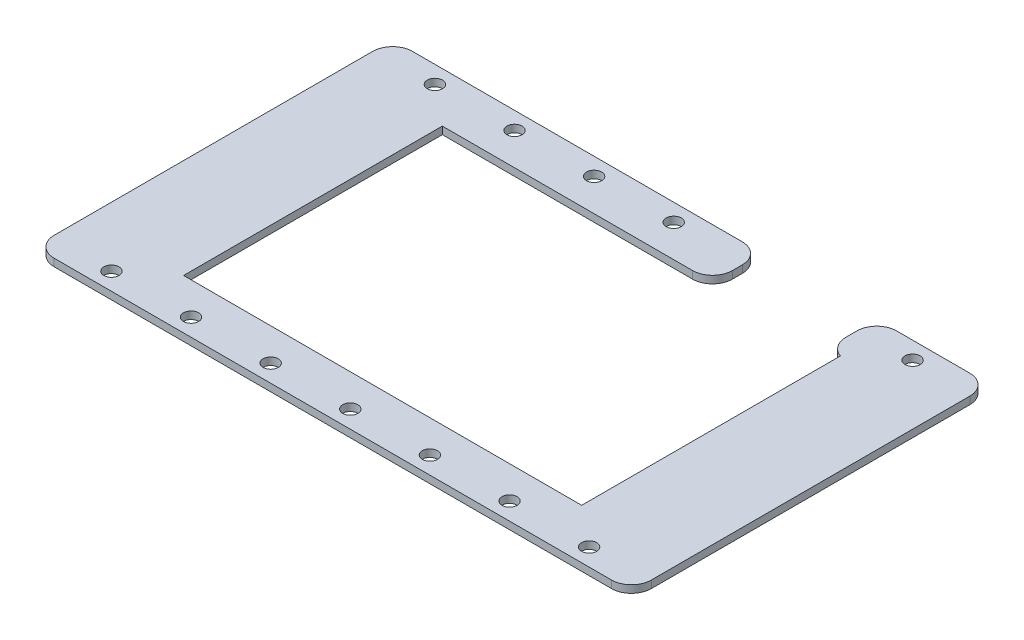
SolidWorks part; units mm, degrees
ref_plane "Front Plane" through (0, 0, 0) normal (0, 0, 1) x (1, 0, 0)
ref_plane "Top Plane" through (0, 0, 0) normal (0, 1, 0) x (1, 0, 0)
ref_plane "Right Plane" through (0, 0, 0) normal (1, 0, 0) x (0, 0, -1)
sketch "Sketch1" plane through (0, 0, 0) normal (0, 1, 0) x (1, 0, 0)
  line L0 (-95.25, -46.0375) -> (95.25, -46.0375) construction
  line L1 (95.25, -57.15) -> (-95.25, -57.15)
  line L2 (95.25, -51.5937) -> (-95.25, -51.5937) construction
  line L3 (95.25, 57.15) -> (-95.25, 57.15)
  line L4 (-95.25, -57.15) -> (-95.25, 57.15)
  line L5 (95.25, -57.15) -> (-95.25, 57.15) construction
  line L6 (95.25, 57.15) -> (-95.25, -57.15) construction
  line L7 (63.5, 41.275) -> (-63.5, 41.275)
  line L8 (63.5, 41.275) -> (63.5, -41.275)
  line L9 (63.5, -41.275) -> (-63.5, -41.275)
  line L10 (-63.5, 41.275) -> (-63.5, -41.275)
  line L11 (63.5, 41.275) -> (-63.5, -41.275) construction
  line L12 (63.5, -41.275) -> (-63.5, 41.275) construction
  line L13 (95.25, -57.15) -> (95.25, 57.15)
  line L14 (-95.25, -57.15) -> (-95.25, -46.0375) construction
  line L15 (95.25, -46.0375) -> (95.25, -57.15) construction
  line L16 (-76.2, -51.5937) -> (-95.25, -46.0375) construction
  line L17 (76.2, -51.5937) -> (95.25, -46.0375) construction
  line L19 (95.25, 0) -> (-95.25, 0) construction
  circle A0 centre (-76.2, -51.5937) radius 2.413
  circle A1 centre (-50.8, -51.5937) radius 2.413
  circle A2 centre (-25.4, -51.5937) radius 2.413
  circle A3 centre (0, -51.5937) radius 2.413
  circle A4 centre (25.4, -51.5937) radius 2.413
  circle A5 centre (50.8, -51.5937) radius 2.413
  circle A6 centre (76.2, -51.5937) radius 2.413
  circle A7 centre (76.2, 51.5938) radius 2.413
  circle A8 centre (50.8, 51.5938) radius 2.413
  circle A9 centre (25.4, 51.5938) radius 2.413
  circle A10 centre (0, 51.5937) radius 2.413
  circle A11 centre (-25.4, 51.5937) radius 2.413
  circle A12 centre (-50.8, 51.5937) radius 2.413
  circle A13 centre (-76.2, 51.5937) radius 2.413
  point P0 (0, 0)
  point P6 (0, 0)
  dimension "D6" = 4.826
  dimension "D7" = 7
  dimension "D8" = 25.4
  dimension "D1" = 114.3
  dimension "D2" = 190.5
  dimension "D3" = 15.875
  dimension "D4" = 31.75
  dimension "D5" = 11.1125
base flange "Base-Flange1" sketch "Sketch1" thickness 2.3813 reverse thickness direction no parameters "D1"=2.3813
fillet "Fillet1" radius 6.35 4 edges at (-95.25, -1.1906, -57.15) (95.25, -1.1906, -57.15) (95.25, -1.1906, 57.15) (-95.25, -1.1906, 57.15)
sketch "Sketch2" plane through (0, 0, 0) normal (0, 1, 0) x (1, 0, 0)
  line L0 (59.215, 41.275) -> (59.215, 57.15)
  line L1 (63.5, 41.275) -> (-63.5, 41.275) construction
  line L2 (88.9, 57.15) -> (-88.9, 57.15) construction
  line L3 (95.25, -50.8) -> (95.25, 50.8) construction
  line L4 (22.6847, 41.275) -> (22.6847, 57.15)
  line L5 (-95.25, 50.8) -> (-95.25, -50.8) construction
  line L6 (59.215, 41.275) -> (22.6847, 41.275)
  line L7 (59.215, 57.15) -> (22.6847, 57.15)
  dimension "D1" = 36.035
  dimension "D2" = 117.9347
extrude "Cut-Extrude1" cut sketch "Sketch2" against normal blind 2.54
fillet "Fillet2" radius 6.35 4 edges at (22.6847, -1.1906, -41.275) (22.6847, -1.1906, -57.15) (59.215, -1.1906, -41.275) (59.215, -1.1906, -57.15)
sketch "Bend-Lines1" plane through (0, 0, 0) normal (0, 1, 0) x (1, 0, 0)
sketch "Bounding-Box1" plane through (0, 0, 0) normal (0, 1, 0) x (1, 0, 0)
sheet metal parameters "Sheet-Metal1" thickness 2.3813 parameters "D1"=2.3813
flat pattern "Flat-Pattern1" [suppressed]
sketch "Bend-Lines2" plane through (0, 0, 0) normal (0, 1, 0) x (1, 0, 0)
sketch "Bounding-Box2" [suppressed] plane through (0, 0, 0) normal (0, 1, 0) x (1, 0, 0)
sheet metal parameters "Sheet-Metal2" thickness 2.3813 parameters "D1"=2.3813
flat pattern "Flat-Pattern1"
sketch "Bend-Lines2" plane through (0, 0, 0) normal (0, 1, 0) x (1, 0, 0)
sketch "Bounding-Box2" [suppressed] plane through (0, 0, 0) normal (0, 1, 0) x (1, 0, 0)
